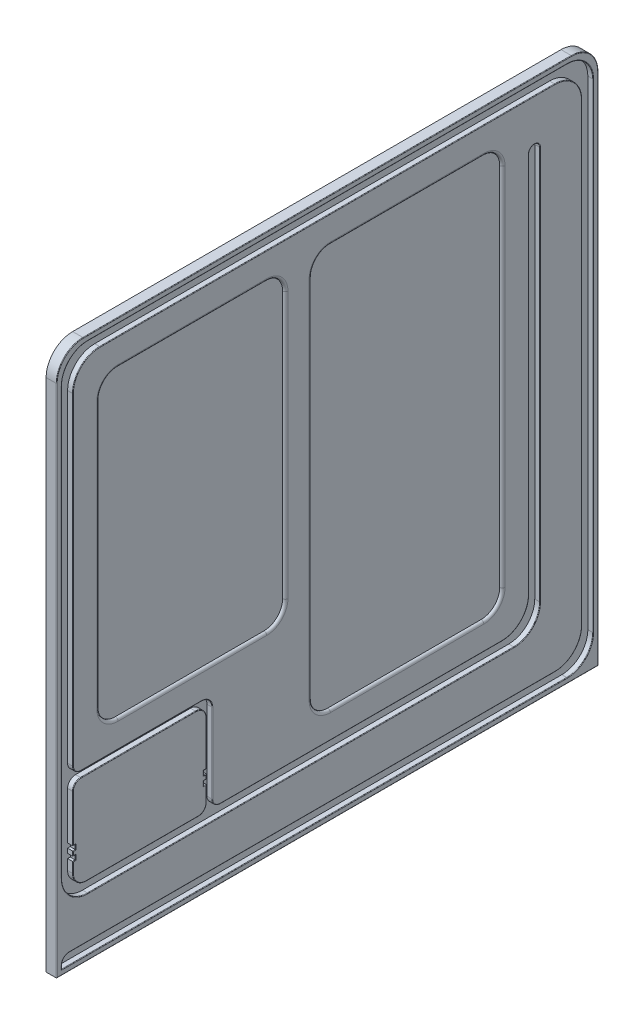
SolidWorks part; units mm, degrees
ref_plane "Front Plane" through (0, 0, 0) normal (0, 0, 1) x (1, 0, 0)
ref_plane "Top Plane" through (0, 0, 0) normal (0, 1, 0) x (1, 0, 0)
ref_plane "Right Plane" through (0, 0, 0) normal (1, 0, 0) x (0, 0, -1)
sketch "Sketch1" plane through (0, 0, 0) normal (1, 0, 0) x (0, 0, -1)
  line L1 (-102, -102) -> (102, -102)
  line L2 (-102, -102) -> (-102, 92)
  line L3 (-92, 102) -> (92, 102)
  line L4 (102, -102) -> (102, 92)
  line L5 (-102, -102) -> (102, 102) construction
  line L6 (-102, 102) -> (102, -102) construction
  arc A2 (-102, 92) -> (-92, 102) centre (-92, 92) cw
  arc A3 (92, 102) -> (102, 92) centre (92, 92) cw
  point P0 (0, 0)
  dimension "D1" = 204
  dimension "D2" = 204
extrude "Boss-Extrude1" add sketch "Sketch1" along normal blind 4
sketch "Sketch2" plane through (4, 0, 0) normal (1, 0, 0) x (0, 0, -1)
  line L40 (-100.1, 90.3) -> (-100.1, -70.3)
  line L41 (-90.3, 100.1) -> (90.3, 100.1)
  line L42 (100.1, 90.3) -> (100.1, -90.3)
  line L43 (90.3, -100.1) -> (-100.1, -100.1)
  line L44 (-100.1, -100.1) -> (-100.1, -98.7)
  line L45 (-97.3, -95.9) -> (85.7, -95.9)
  line L46 (85.7, 95.9) -> (-85.7, 95.9)
  line L47 (-95.9, 85.7) -> (-95.9, -35.9)
  line L48 (-90.9, -75.9) -> (-48.6, -75.9)
  line L49 (75.9, -65.7) -> (75.9, 78)
  line L50 (-90.3, -80.1) -> (70.3, -80.1)
  line L51 (95.9, -85.7) -> (95.9, 85.7)
  line L52 (80.1, 78) -> (80.1, -70.3)
  line L55 (-92.9, -41.1) -> (-49.6, -41.1)
  line L56 (-45.6, -45.1) -> (-45.6, -61.9)
  line L57 (-43.4, -72.9) -> (-43.4, -42.9)
  line L58 (-47.4, -38.9) -> (-92.9, -38.9)
  line L59 (-95.9, -44.1) -> (-95.9, -61.9)
  line L60 (-40.4, -75.9) -> (65.7, -75.9)
  line L61 (-95.9, -61.9) -> (-94.9, -61.9)
  line L62 (-94.9, -61.9) -> (-94.9, -63.6)
  line L63 (-94.9, -63.6) -> (-95.9, -63.6)
  line L64 (-95.9, -65.3) -> (-94.9, -65.3)
  line L65 (-94.9, -65.3) -> (-94.9, -67)
  line L66 (-94.9, -67) -> (-95.9, -67)
  line L67 (-95.9, -63.6) -> (-95.9, -65.3)
  line L68 (-95.9, -67) -> (-95.9, -70.9)
  line L69 (-45.6, -61.9) -> (-46.6, -61.9)
  line L70 (-46.6, -61.9) -> (-46.6, -63.6)
  line L71 (-46.6, -63.6) -> (-45.6, -63.6)
  line L72 (-45.6, -67) -> (-46.6, -67)
  line L73 (-46.6, -67) -> (-46.6, -65.3)
  line L74 (-46.6, -65.3) -> (-45.6, -65.3)
  line L75 (-45.6, -63.6) -> (-45.6, -65.3)
  line L76 (-45.6, -67) -> (-45.6, -72.9)
  line L77 (92, 102) -> (-92, 102) construction
  line L78 (-102, 92) -> (-102, -102) construction
  arc A32 (-95.9, -70.9) -> (-90.9, -75.9) centre (-90.9, -70.9) ccw
  arc A33 (65.7, -75.9) -> (75.9, -65.7) centre (65.7, -65.7) ccw
  arc A34 (-85.7, 95.9) -> (-95.9, 85.7) centre (-85.7, 85.7) ccw
  arc A35 (-100.1, 90.3) -> (-90.3, 100.1) centre (-90.3, 90.3) cw
  arc A36 (100.1, -90.3) -> (90.3, -100.1) centre (90.3, -90.3) cw
  arc A37 (85.7, -95.9) -> (95.9, -85.7) centre (85.7, -85.7) ccw
  arc A38 (80.1, -70.3) -> (70.3, -80.1) centre (70.3, -70.3) cw
  arc A39 (85.7, 95.9) -> (95.9, 85.7) centre (85.7, 85.7) cw
  arc A40 (90.3, 100.1) -> (100.1, 90.3) centre (90.3, 90.3) cw
  arc A41 (75.9, 78) -> (80.1, 78) centre (78, 78) cw
  arc A42 (-100.1, -98.7) -> (-97.3, -95.9) centre (-97.3, -98.7) cw
  arc A43 (-100.1, -70.3) -> (-90.3, -80.1) centre (-90.3, -70.3) ccw
  arc A44 (-43.4, -42.9) -> (-47.4, -38.9) centre (-47.4, -42.9) ccw
  arc A45 (-49.6, -41.1) -> (-45.6, -45.1) centre (-49.6, -45.1) cw
  arc A46 (-40.4, -75.9) -> (-43.4, -72.9) centre (-40.4, -72.9) cw
  arc A47 (-92.9, -38.9) -> (-95.9, -35.9) centre (-92.9, -35.9) cw
  arc A48 (-45.6, -72.9) -> (-48.6, -75.9) centre (-48.6, -72.9) cw
  arc A49 (-92.9, -41.1) -> (-95.9, -44.1) centre (-92.9, -44.1) ccw
  point P107 (-95.4, -65.3)
  dimension "D26" = 4.2
  dimension "D27" = 10.2
  dimension "D9" = 34.8
  dimension "D35" = 9.8
  dimension "D30" = 10.2
  dimension "D31" = 9.8
  dimension "D41" = 10.2
  dimension "D42" = 9.8
  dimension "D43" = 10.2
  dimension "D44" = 9.8
  dimension "D47" = 2.8
  dimension "D48" = 9.8
  dimension "D49" = 5
  dimension "D52" = 4
  dimension "D53" = 3
  dimension "D54" = 3
  dimension "D1" = 1.9
  dimension "D7" = 1.9
  dimension "D8" = 50.3
  dimension "D21" = 4.2
  dimension "D22" = 4.2
  dimension "D23" = 4.2
  dimension "D25" = 15.8
  dimension "D36" = 200.2
  dimension "D37" = 200.2
  dimension "D38" = 4.2
  dimension "D39" = 15.8
  dimension "D40" = 4.2
  dimension "D45" = 2.1
  dimension "D46" = 15.8
  dimension "D50" = 2.2
  dimension "D51" = 2.2
  dimension "D55" = 1.7
  dimension "D56" = 1.7
  dimension "D57" = 1
  dimension "D58" = 20.8
extrude "Cut-Extrude3" cut sketch "Sketch2" against normal blind 2
fillet "Fillet1" radius 0.2 59 edges at (4, -102, 0) (4, -5, 102) (4, 99.0711, 99.0711) (4, 102, 0) (4, 99.0711, -99.0711) (4, -5, -102) (4, -72.9125, -72.9125) (4, -75.9, -12.65) (4, -75.0213, 42.5213) (4, -57.9, 43.4) (4, -40.0716, 44.5716) (4, -38.9, 70.15) (4, -38.0213, 95.0213) (4, 24.9, 95.9) (4, 92.9125, 92.9125) (4, 95.9, 0) (4, 92.9125, -92.9125) (4, 0, -95.9) (4, -92.9125, -92.9125) (4, -95.9, 5.8) (4, -96.7201, 99.2799) (4, -99.4, 100.1) (4, -100.1, 4.9) (4, -97.2296, -97.2296) (4, 0, -100.1) (4, 97.2296, -97.2296) (4, 100.1, 0) (4, 97.2296, 97.2296) (4, 10, 100.1) (4, -77.2296, 97.2296) (4, -80.1, 10) (4, -77.2296, -77.2296) (4, 3.85, -80.1) (4, 80.1, -78) (4, 6.15, -75.9) (4, -68.95, 95.9) (4, -67, 95.4) (4, -66.15, 94.9) (4, -65.3, 95.4) (4, -64.45, 95.9) (4, -63.6, 95.4) (4, -62.75, 94.9) (4, -61.9, 95.4) (4, -53, 95.9) (4, -41.9787, 95.0213) (4, -41.1, 71.25) (4, -42.2716, 46.7716) (4, -53.5, 45.6) (4, -61.9, 46.1) (4, -62.75, 46.6) (4, -63.6, 46.1) (4, -64.45, 45.6) (4, -65.3, 46.1) (4, -66.15, 46.6) (4, -67, 46.1) (4, -69.95, 45.6) (4, -75.0213, 46.4787) (4, -75.9, 69.75) (4, -74.4355, 94.4355)
sketch "Sketch3" plane through (4, 0, 0) normal (1, 0, 0) x (0, 0, -1)
  line L0 (85.7, 95.7) -> (-85.7, 95.7) construction
  line L1 (-78.9, -28.7) -> (-22.9, -28.7)
  line L2 (-85.9, -21.7) -> (-85.9, 78.7)
  line L3 (-78.9, 85.7) -> (-22.9, 85.7)
  line L4 (-15.9, -21.7) -> (-15.9, 78.7)
  line L5 (-85.9, -28.7) -> (-15.9, 85.7) construction
  line L6 (-85.9, 85.7) -> (-15.9, -28.7) construction
  line L7 (1.1, -65.9) -> (58.9, -65.9)
  line L8 (-5.9, -58.9) -> (-5.9, 78.7)
  line L9 (1.1, 85.7) -> (58.9, 85.7)
  line L10 (65.9, -58.9) -> (65.9, 78.7)
  line L11 (-5.9, -65.9) -> (65.9, 85.7) construction
  line L12 (-5.9, 85.7) -> (65.9, -65.9) construction
  line L13 (65.7, -75.9) -> (-40.4, -75.9) construction
  line L14 (75.9, 78) -> (75.9, -65.7) construction
  line L15 (-95.9, -35.9) -> (-95.9, 85.7) construction
  line L16 (-92.9, -38.7) -> (-47.4, -38.7) construction
  arc A0 (-22.9, 85.7) -> (-15.9, 78.7) centre (-22.9, 78.7) cw
  arc A1 (-85.9, 78.7) -> (-78.9, 85.7) centre (-78.9, 78.7) cw
  arc A2 (-78.9, -28.7) -> (-85.9, -21.7) centre (-78.9, -21.7) cw
  arc A3 (-22.9, -28.7) -> (-15.9, -21.7) centre (-22.9, -21.7) ccw
  arc A4 (58.9, -65.9) -> (65.9, -58.9) centre (58.9, -58.9) ccw
  arc A5 (1.1, -65.9) -> (-5.9, -58.9) centre (1.1, -58.9) cw
  arc A6 (-5.9, 78.7) -> (1.1, 85.7) centre (1.1, 78.7) cw
  arc A7 (58.9, 85.7) -> (65.9, 78.7) centre (58.9, 78.7) cw
  point P0 (-50.9, 28.5)
  point P5 (30, 9.9)
  dimension "D9" = 7
  dimension "D1" = 10
  dimension "D2" = 10
  dimension "D3" = 10
  dimension "D4" = 10
  dimension "D5" = 10
  dimension "D6" = 10
  dimension "D7" = 10
  dimension "D8" = 70
extrude "Cut-Extrude4" cut sketch "Sketch3" against normal blind 1
fillet "Fillet2" radius 1 16 edges at (4, 83.6497, -63.8497) (4, 9.9, -65.9) (4, -63.8497, -63.8497) (4, -65.9, -30) (4, -63.8497, 3.8497) (4, 9.9, 5.9) (4, 83.6497, 3.8497) (4, 83.6497, 17.9503) (4, 28.5, 15.9) (4, -26.6497, 17.9503) (4, -28.7, 50.9) (4, -26.6497, 83.8497) (4, 28.5, 85.9) (4, 83.6497, 83.8497) (4, 85.7, -30) (4, 85.7, 50.9)
